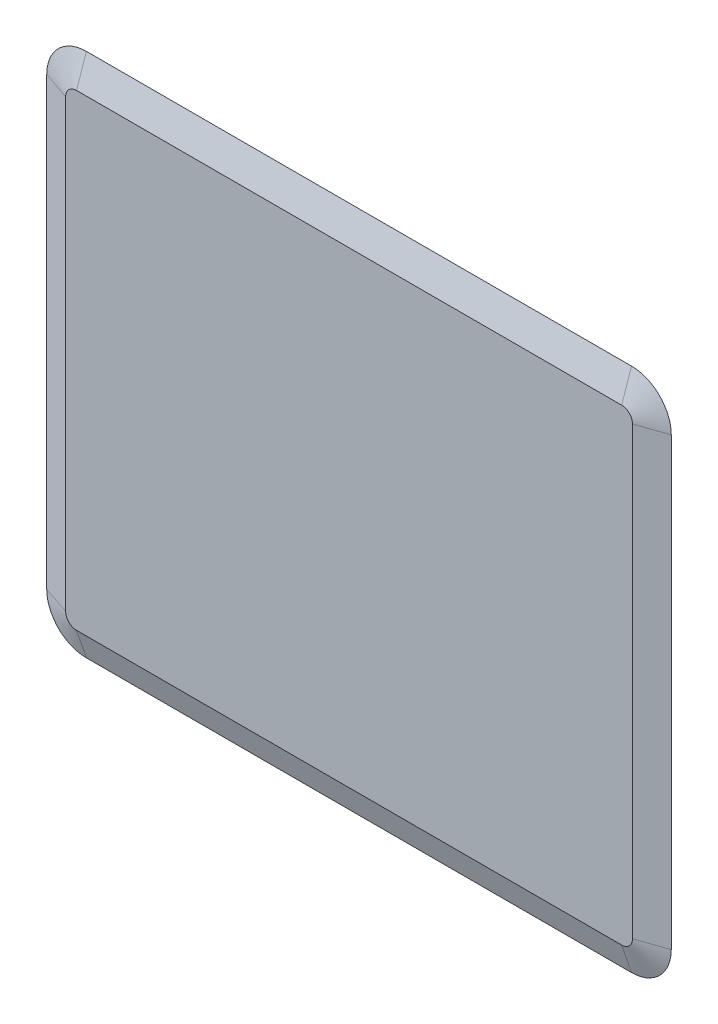
SolidWorks part; units mm, degrees
ref_plane "Front Plane" through (0, 0, 0) normal (0, 0, 1) x (1, 0, 0)
ref_plane "Top Plane" through (0, 0, 0) normal (0, 1, 0) x (1, 0, 0)
ref_plane "Right Plane" through (0, 0, 0) normal (1, 0, 0) x (0, 0, -1)
sketch "Sketch1" plane through (0, 0, 0) normal (0, 0, 1) x (1, 0, 0)
  line L1 (-24.35, -23.45) -> (24.35, -23.45)
  line L2 (-28.45, -19.35) -> (-28.45, 19.35)
  line L3 (-24.35, 23.45) -> (24.35, 23.45)
  line L4 (28.45, -19.35) -> (28.45, 19.35)
  line L5 (-28.45, -23.45) -> (28.45, 23.45) construction
  line L6 (-28.45, 23.45) -> (28.45, -23.45) construction
  arc A0 (-28.45, 19.35) -> (-24.35, 23.45) centre (-24.35, 19.35) cw
  arc A1 (-24.35, -23.45) -> (-28.45, -19.35) centre (-24.35, -19.35) cw
  arc A2 (24.35, -23.45) -> (28.45, -19.35) centre (24.35, -19.35) ccw
  arc A3 (24.35, 23.45) -> (28.45, 19.35) centre (24.35, 19.35) cw
  point P0 (0, 0)
  dimension "D1" = 4.1
  dimension "D2" = 56.9
  dimension "D3" = 46.9
extrude "Boss-Extrude1" add sketch "Sketch1" along normal blind 3
sketch "Sketch2" plane through (0, 0, 3) normal (0, 0, 1) x (1, 0, 0)
  line L0 (28.45, -19.35) -> (28.45, 19.35) construction
  line L1 (-27.45, -26.45) -> (27.45, -26.45)
  line L2 (-31.45, -22.45) -> (-31.45, 22.45)
  line L3 (-27.45, 26.45) -> (27.45, 26.45)
  line L4 (31.45, -22.45) -> (31.45, 22.45)
  line L5 (-31.45, -26.45) -> (31.45, 26.45) construction
  line L6 (-31.45, 26.45) -> (31.45, -26.45) construction
  line L7 (24.35, 23.45) -> (-24.35, 23.45) construction
  arc A0 (-31.45, 22.45) -> (-27.45, 26.45) centre (-27.45, 22.45) cw
  arc A1 (-27.45, -26.45) -> (-31.45, -22.45) centre (-27.45, -22.45) cw
  arc A2 (27.45, -26.45) -> (31.45, -22.45) centre (27.45, -22.45) ccw
  arc A3 (27.45, 26.45) -> (31.45, 22.45) centre (27.45, 22.45) cw
  point P0 (0, 0)
  dimension "D3" = 4
  dimension "D1" = 3
  dimension "D2" = 3
extrude "Boss-Extrude2" add sketch "Sketch2" along normal blind 1
chamfer "Chamfer1" distance 1 angle 71 8 edges at (0, 26.45, 4) (30.2784, 25.2784, 4) (31.45, 0, 4) (30.2784, -25.2784, 4) (0, -26.45, 4) (-30.2784, -25.2784, 4) (-31.45, 0, 4) (-30.2784, 25.2784, 4) first distance on face at (0, 26.45, 3.5) first distance on face at (29.8642, 24.8642, 3.5) first distance on face at (31.45, 0, 3.5) first distance on face at (29.8642, -24.8642, 3.5) first distance on face at (0, -26.45, 3.5) first distance on face at (-29.8642, -24.8642, 3.5) first distance on face at (-31.45, 0, 3.5) first distance on face at (-29.8642, 24.8642, 3.5)
sketch "Sketch3" plane through (0, 0, 0) normal (0, 0, -1) x (-1, 0, 0)
  line L0 (28.45, 19.35) -> (28.45, -19.35) construction
  line L1 (-22.45, -21.45) -> (22.45, -21.45)
  line L2 (-26.45, -17.45) -> (-26.45, 17.45)
  line L3 (-22.45, 21.45) -> (22.45, 21.45)
  line L4 (26.45, -17.45) -> (26.45, 17.45)
  line L5 (-26.45, -21.45) -> (26.45, 21.45) construction
  line L6 (-26.45, 21.45) -> (26.45, -21.45) construction
  line L7 (-24.35, 23.45) -> (24.35, 23.45) construction
  arc A0 (22.45, -21.45) -> (26.45, -17.45) centre (22.45, -17.45) ccw
  arc A1 (-22.45, -21.45) -> (-26.45, -17.45) centre (-22.45, -17.45) cw
  arc A2 (-26.45, 17.45) -> (-22.45, 21.45) centre (-22.45, 17.45) cw
  arc A3 (22.45, 21.45) -> (26.45, 17.45) centre (22.45, 17.45) cw
  point P0 (0, 0)
  dimension "D1" = 4
  dimension "D2" = 2
  dimension "D3" = 2
extrude "Cut-Extrude1" cut sketch "Sketch3" against normal blind 3
